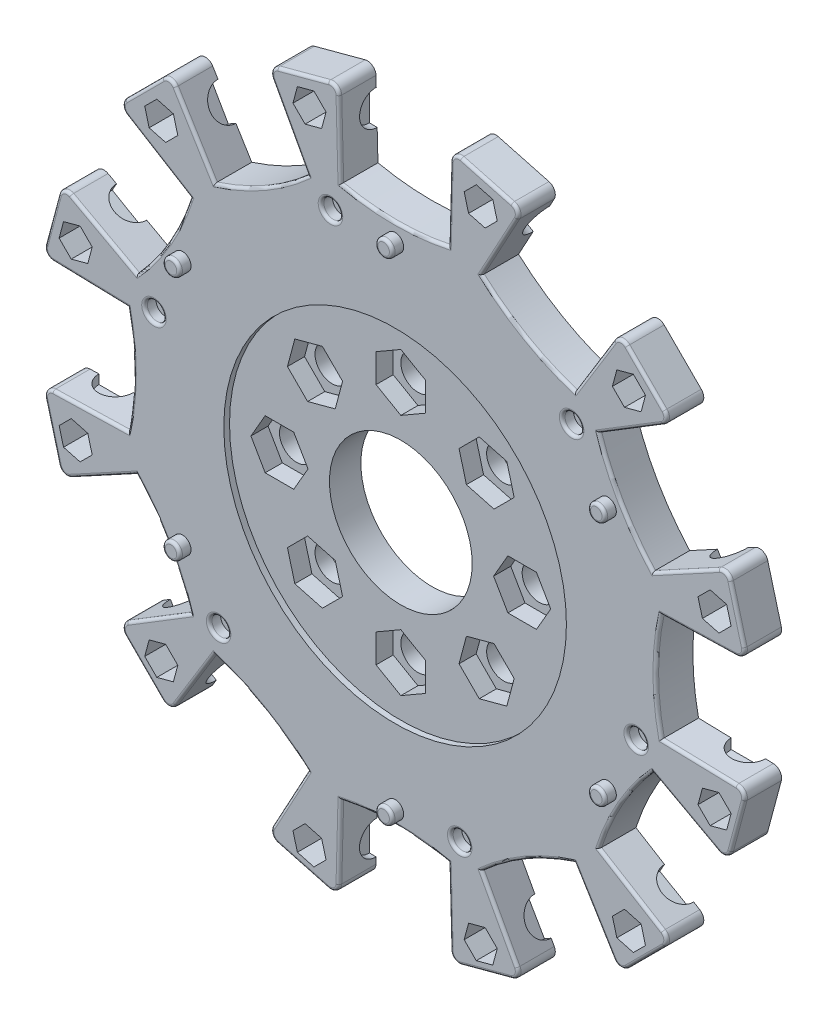
SolidWorks part; units mm, degrees
ref_plane "Front Plane" through (0, 0, 0) normal (0, 0, 1) x (1, 0, 0)
ref_plane "Top Plane" through (0, 0, 0) normal (0, 1, 0) x (1, 0, 0)
ref_plane "Right Plane" through (0, 0, 0) normal (1, 0, 0) x (0, 0, -1)
sketch "Sketch1" plane through (0, 0, 0) normal (0, 0, 1) x (1, 0, 0)
  line L0 (-87.8157, 0) -> (95.9972, 0) construction
  line L1 (0, 160.1388) -> (0, -68.1388) construction
  line L2 (-22.4547, 58.688) -> (-9.8977, 62.0527)
  line L3 (-15.2988, 45.505) -> (-9.5033, 47.0579) construction
  line L4 (-9.8977, 62.0527) -> (-9.5033, 47.0579)
  line L5 (-22.4547, 58.688) -> (-15.2988, 45.505)
  line L6 (22.2778, 58.688) -> (15.1219, 45.505)
  line L7 (9.7207, 62.0527) -> (22.2778, 58.688)
  line L8 (9.7207, 62.0527) -> (9.3264, 47.0579)
  line L9 (48.4602, 39.6864) -> (35.6715, 31.8475)
  line L10 (39.2678, 48.8788) -> (48.4602, 39.6864)
  line L11 (39.2678, 48.8788) -> (31.4289, 36.0901)
  line L12 (61.6341, 10.1394) -> (46.6392, 9.745)
  line L13 (58.2694, 22.6964) -> (61.6341, 10.1394)
  line L14 (58.2694, 22.6964) -> (45.0863, 15.5405)
  line L15 (58.2694, -22.0361) -> (45.0863, -14.8802)
  line L16 (61.6341, -9.479) -> (58.2694, -22.0361)
  line L17 (61.6341, -9.479) -> (46.6392, -9.0847)
  line L18 (39.2678, -48.2185) -> (31.4289, -35.4298)
  line L19 (48.4602, -39.0261) -> (39.2678, -48.2185)
  line L20 (48.4602, -39.0261) -> (35.6715, -31.1872)
  line L21 (9.7207, -61.3923) -> (9.3264, -46.3975)
  line L22 (22.2778, -58.0277) -> (9.7207, -61.3923)
  line L23 (22.2778, -58.0277) -> (15.1219, -44.8446)
  line L24 (-22.4547, -58.0277) -> (-15.2988, -44.8446)
  line L25 (-9.8977, -61.3923) -> (-22.4547, -58.0277)
  line L26 (-9.8977, -61.3923) -> (-9.5033, -46.3975)
  line L27 (-48.6371, -39.0261) -> (-35.8484, -31.1872)
  line L28 (-39.4447, -48.2185) -> (-48.6371, -39.0261)
  line L29 (-39.4447, -48.2185) -> (-31.6058, -35.4298)
  line L30 (-61.811, -9.479) -> (-46.8162, -9.0847)
  line L31 (-58.4463, -22.0361) -> (-61.811, -9.479)
  line L32 (-58.4463, -22.0361) -> (-45.2633, -14.8802)
  line L33 (-58.4463, 22.6964) -> (-45.2633, 15.5405)
  line L34 (-61.811, 10.1394) -> (-58.4463, 22.6964)
  line L35 (-61.811, 10.1394) -> (-46.8162, 9.745)
  line L36 (-39.4447, 48.8788) -> (-31.6058, 36.0901)
  line L37 (-48.6371, 39.6864) -> (-39.4447, 48.8788)
  line L38 (-48.6371, 39.6864) -> (-35.8484, 31.8475)
  line L39 (12.8679, 53.8194) -> (15.7657, 53.0429)
  line L40 (-12.0915, 56.7171) -> (-14.2128, 58.8385)
  line L41 (-14.2128, 58.8385) -> (-17.1106, 58.062)
  line L42 (-17.1106, 58.062) -> (-17.887, 55.1642)
  line L43 (-17.887, 55.1642) -> (-15.7657, 53.0429)
  line L44 (-15.7657, 53.0429) -> (-12.8679, 53.8194)
  line L45 (-12.8679, 53.8194) -> (-12.0915, 56.7171)
  line L46 (15.7657, 53.0429) -> (17.887, 55.1642)
  line L47 (17.887, 55.1642) -> (17.1106, 58.062)
  line L48 (17.1106, 58.062) -> (14.2128, 58.8385)
  line L49 (14.2128, 58.8385) -> (12.0915, 56.7171)
  line L50 (12.0915, 56.7171) -> (12.8679, 53.8194)
  line L51 (38.0536, 40.175) -> (40.175, 38.0536)
  line L52 (40.175, 38.0536) -> (43.0727, 38.8301)
  line L53 (43.0727, 38.8301) -> (43.8492, 41.7279)
  line L54 (43.8492, 41.7279) -> (41.7279, 43.8492)
  line L55 (41.7279, 43.8492) -> (38.8301, 43.0727)
  line L56 (38.8301, 43.0727) -> (38.0536, 40.175)
  line L57 (53.0429, 15.7657) -> (53.8194, 12.8679)
  line L58 (53.8194, 12.8679) -> (56.7171, 12.0915)
  line L59 (56.7171, 12.0915) -> (58.8385, 14.2128)
  line L60 (58.8385, 14.2128) -> (58.062, 17.1106)
  line L61 (58.062, 17.1106) -> (55.1642, 17.887)
  line L62 (55.1642, 17.887) -> (53.0429, 15.7657)
  line L63 (53.8194, -12.8679) -> (53.0429, -15.7657)
  line L64 (53.0429, -15.7657) -> (55.1642, -17.887)
  line L65 (55.1642, -17.887) -> (58.062, -17.1106)
  line L66 (58.062, -17.1106) -> (58.8385, -14.2128)
  line L67 (58.8385, -14.2128) -> (56.7171, -12.0915)
  line L68 (56.7171, -12.0915) -> (53.8194, -12.8679)
  line L69 (40.175, -38.0536) -> (38.0536, -40.175)
  line L70 (38.0536, -40.175) -> (38.8301, -43.0727)
  line L71 (38.8301, -43.0727) -> (41.7279, -43.8492)
  line L72 (41.7279, -43.8492) -> (43.8492, -41.7279)
  line L73 (43.8492, -41.7279) -> (43.0727, -38.8301)
  line L74 (43.0727, -38.8301) -> (40.175, -38.0536)
  line L75 (15.7657, -53.0429) -> (12.8679, -53.8194)
  line L76 (12.8679, -53.8194) -> (12.0915, -56.7171)
  line L77 (12.0915, -56.7171) -> (14.2128, -58.8385)
  line L78 (14.2128, -58.8385) -> (17.1106, -58.062)
  line L79 (17.1106, -58.062) -> (17.887, -55.1642)
  line L80 (17.887, -55.1642) -> (15.7657, -53.0429)
  line L81 (-12.8679, -53.8194) -> (-15.7657, -53.0429)
  line L82 (-15.7657, -53.0429) -> (-17.887, -55.1642)
  line L83 (-17.887, -55.1642) -> (-17.1106, -58.062)
  line L84 (-17.1106, -58.062) -> (-14.2128, -58.8385)
  line L85 (-14.2128, -58.8385) -> (-12.0915, -56.7171)
  line L86 (-12.0915, -56.7171) -> (-12.8679, -53.8194)
  line L87 (-38.0536, -40.175) -> (-40.175, -38.0536)
  line L88 (-40.175, -38.0536) -> (-43.0727, -38.8301)
  line L89 (-43.0727, -38.8301) -> (-43.8492, -41.7279)
  line L90 (-43.8492, -41.7279) -> (-41.7279, -43.8492)
  line L91 (-41.7279, -43.8492) -> (-38.8301, -43.0727)
  line L92 (-38.8301, -43.0727) -> (-38.0536, -40.175)
  line L93 (-53.0429, -15.7657) -> (-53.8194, -12.8679)
  line L94 (-53.8194, -12.8679) -> (-56.7171, -12.0915)
  line L95 (-56.7171, -12.0915) -> (-58.8385, -14.2128)
  line L96 (-58.8385, -14.2128) -> (-58.062, -17.1106)
  line L97 (-58.062, -17.1106) -> (-55.1642, -17.887)
  line L98 (-55.1642, -17.887) -> (-53.0429, -15.7657)
  line L99 (-53.8194, 12.8679) -> (-53.0429, 15.7657)
  line L100 (-53.0429, 15.7657) -> (-55.1642, 17.887)
  line L101 (-55.1642, 17.887) -> (-58.062, 17.1106)
  line L102 (-58.062, 17.1106) -> (-58.8385, 14.2128)
  line L103 (-58.8385, 14.2128) -> (-56.7171, 12.0915)
  line L104 (-56.7171, 12.0915) -> (-53.8194, 12.8679)
  line L105 (-40.175, 38.0536) -> (-38.0536, 40.175)
  line L106 (-38.0536, 40.175) -> (-38.8301, 43.0727)
  line L107 (-38.8301, 43.0727) -> (-41.7279, 43.8492)
  line L108 (-41.7279, 43.8492) -> (-43.8492, 41.7279)
  line L109 (-43.8492, 41.7279) -> (-43.0727, 38.8301)
  line L110 (-43.0727, 38.8301) -> (-40.175, 38.0536)
  circle A0 centre (0, 0) radius 62.5 construction
  arc A2 (-9.5033, 47.0579) -> (9.3264, 47.0579) centre (-0.0885, 91.062) ccw
  arc A3 (15.1219, 45.505) -> (31.4289, 36.0901) centre (45.2774, 78.9062) ccw
  arc A4 (35.6715, 31.8475) -> (45.0863, 15.5405) centre (78.4876, 45.6961) ccw
  arc A5 (46.6392, 9.745) -> (46.6392, -9.0847) centre (90.6433, 0.3302) ccw
  arc A6 (45.0863, -14.8802) -> (35.6715, -31.1872) centre (78.4876, -45.0357) ccw
  arc A7 (31.4289, -35.4298) -> (15.1219, -44.8446) centre (45.2774, -78.2459) ccw
  arc A8 (9.3264, -46.3975) -> (-9.5033, -46.3975) centre (-0.0885, -90.4016) ccw
  arc A9 (-15.2988, -44.8446) -> (-31.6058, -35.4298) centre (-45.4544, -78.2459) ccw
  arc A10 (-35.8484, -31.1872) -> (-45.2633, -14.8802) centre (-78.6645, -45.0357) ccw
  arc A11 (-46.8162, -9.0847) -> (-46.8162, 9.745) centre (-90.8203, 0.3302) ccw
  arc A12 (-45.2633, 15.5405) -> (-35.8484, 31.8475) centre (-78.6645, 45.6961) ccw
  arc A13 (-31.6058, 36.0901) -> (-15.2988, 45.505) centre (-45.4544, 78.9062) ccw
  circle A14 centre (-14.9893, 55.9407) radius 2.5981 construction
  point P10 (-16.1762, 60.3704)
  point P12 (-16.1762, 60.3704)
  point P14 (-12.4011, 46.2814)
  dimension "D1" = 125
  dimension "D3" = 6
  dimension "D2" = 15
  dimension "D5" = 45
  dimension "D4" = 12
  dimension "D6" = 13
  dimension "D8" = 10
  dimension "D9" = 3
  dimension "D7" = 12
  dimension "D10" = 12
extrude "Boss-Extrude1" add sketch "Sketch1" along normal blind 6.5
sketch "Sketch5" plane through (0, 0, 0) normal (0, 0, -1) x (-1, 0, 0)
  line L0 (0, 0) -> (0, 67.5888) construction
  line L2 (-11, 58.3612) -> (11, 58.3612)
  line L3 (-11, 58.3612) -> (-11, 55.3612)
  line L4 (-11, 55.3612) -> (11, 55.3612)
  line L5 (11, 58.3612) -> (11, 55.3612)
  point P3 (0, 56.8612)
  dimension "D1" = 22
  dimension "D2" = 3
revolve "Cut-Revolve2" cut sketch "Sketch5" angle 360 about L4
fillet "Fillet1" radius 1.5 24 edges at (9.7207, 62.0527, 3.25) (22.2778, 58.688, 3.25) (39.2678, 48.8788, 3.25) (48.4602, 39.6864, 3.25) (58.2694, 22.6964, 3.25) (61.6341, 10.1394, 3.25) (61.6341, -9.479, 3.25) (58.2694, -22.0361, 3.25) (48.4602, -39.0261, 3.25) (39.2678, -48.2185, 3.25) (22.2778, -58.0277, 3.25) (9.7207, -61.3923, 3.25) (-9.8977, -61.3923, 3.25) (-22.4547, -58.0277, 3.25) (-39.4447, -48.2185, 3.25) (-48.6371, -39.0261, 3.25) (-58.4463, -22.0361, 3.25) (-61.811, -9.479, 3.25) (-61.811, 10.1394, 3.25) (-58.4463, 22.6964, 3.25) (-48.6371, 39.6864, 3.25) (-39.4447, 48.8788, 3.25) (-22.4547, 58.688, 3.25) (-9.8977, 62.0527, 3.25)
sketch "Sketch6" plane through (0, 0, 6.5) normal (0, 0, 1) x (1, 0, 0)
  line L0 (0, 12.5) -> (0, 30) construction
  line L1 (19.8556, 13.7319) -> (18.5616, 18.5616)
  line L2 (4.3301, 23.75) -> (0, 26.25)
  line L3 (0, 26.25) -> (-4.3301, 23.75)
  line L4 (-4.3301, 23.75) -> (-4.3301, 18.75)
  line L5 (-4.3301, 18.75) -> (0, 16.25)
  line L6 (0, 16.25) -> (4.3301, 18.75)
  line L7 (4.3301, 18.75) -> (4.3301, 23.75)
  line L8 (18.5616, 18.5616) -> (13.7319, 19.8556)
  line L9 (13.7319, 19.8556) -> (10.1964, 16.3201)
  line L10 (10.1964, 16.3201) -> (11.4905, 11.4905)
  line L11 (11.4905, 11.4905) -> (16.3201, 10.1964)
  line L12 (16.3201, 10.1964) -> (19.8556, 13.7319)
  line L13 (23.75, -4.3301) -> (26.25, 0)
  line L14 (26.25, 0) -> (23.75, 4.3301)
  line L15 (23.75, 4.3301) -> (18.75, 4.3301)
  line L16 (18.75, 4.3301) -> (16.25, 0)
  line L17 (16.25, 0) -> (18.75, -4.3301)
  line L18 (18.75, -4.3301) -> (23.75, -4.3301)
  line L19 (13.7319, -19.8556) -> (18.5616, -18.5616)
  line L20 (18.5616, -18.5616) -> (19.8556, -13.7319)
  line L21 (19.8556, -13.7319) -> (16.3201, -10.1964)
  line L22 (16.3201, -10.1964) -> (11.4905, -11.4905)
  line L23 (11.4905, -11.4905) -> (10.1964, -16.3201)
  line L24 (10.1964, -16.3201) -> (13.7319, -19.8556)
  line L25 (-4.3301, -23.75) -> (0, -26.25)
  line L26 (0, -26.25) -> (4.3301, -23.75)
  line L27 (4.3301, -23.75) -> (4.3301, -18.75)
  line L28 (4.3301, -18.75) -> (0, -16.25)
  line L29 (0, -16.25) -> (-4.3301, -18.75)
  line L30 (-4.3301, -18.75) -> (-4.3301, -23.75)
  line L31 (-19.8556, -13.7319) -> (-18.5616, -18.5616)
  line L32 (-18.5616, -18.5616) -> (-13.7319, -19.8556)
  line L33 (-13.7319, -19.8556) -> (-10.1964, -16.3201)
  line L34 (-10.1964, -16.3201) -> (-11.4905, -11.4905)
  line L35 (-11.4905, -11.4905) -> (-16.3201, -10.1964)
  line L36 (-16.3201, -10.1964) -> (-19.8556, -13.7319)
  line L37 (-23.75, 4.3301) -> (-26.25, 0)
  line L38 (-26.25, 0) -> (-23.75, -4.3301)
  line L39 (-23.75, -4.3301) -> (-18.75, -4.3301)
  line L40 (-18.75, -4.3301) -> (-16.25, 0)
  line L41 (-16.25, 0) -> (-18.75, 4.3301)
  line L42 (-18.75, 4.3301) -> (-23.75, 4.3301)
  line L43 (-13.7319, 19.8556) -> (-18.5616, 18.5616)
  line L44 (-18.5616, 18.5616) -> (-19.8556, 13.7319)
  line L45 (-19.8556, 13.7319) -> (-16.3201, 10.1964)
  line L46 (-16.3201, 10.1964) -> (-11.4905, 11.4905)
  line L47 (-11.4905, 11.4905) -> (-10.1964, 16.3201)
  line L48 (-10.1964, 16.3201) -> (-13.7319, 19.8556)
  circle A0 centre (0, 0) radius 12.5
  circle A1 centre (0, 0) radius 30
  circle A2 centre (0, 21.25) radius 4.3301 construction
  circle A3 centre (0, 21.25) radius 3
  circle A4 centre (15.026, 15.026) radius 3
  circle A5 centre (21.25, 0) radius 3
  circle A6 centre (15.026, -15.026) radius 3
  circle A7 centre (0, -21.25) radius 3
  circle A8 centre (-15.026, -15.026) radius 3
  circle A9 centre (-21.25, 0) radius 3
  circle A10 centre (-15.026, 15.026) radius 3
  dimension "D1" = 60
  dimension "D2" = 25
  dimension "D4" = 6
  dimension "D5" = 5
  dimension "D3" = 8
  dimension "D6" = 8
extrude "Cut-Extrude1" cut sketch "Sketch6" against normal through all contours A0 | A3 | A4 | A5 | A6 | A7 | A8 | A9 | A10 region at (0, 0, 6.5) region at (0, 21.25, 6.5) region at (15.026, 15.026, 6.5) region at (21.25, 0, 6.5) region at (15.026, -15.026, 6.5) region at (0, -21.25, 6.5) region at (-15.026, -15.026, 6.5) region at (-21.25, 0, 6.5) region at (-15.026, 15.026, 6.5)
extrude "Cut-Extrude2" cut sketch "Sketch6<3>" against normal blind 1 contours A1 L7 L6 L5 L4 L3 L2 L12 L11 L10 L9 L8 L1 L18 L17 L16 L15 L14 L13 L24 L23 L22 L21 L20 L19 L30 L29 L28 L27 L26 L25 L36 L35 L34 L33 L32 L31 L42 L41 L40 L39 L38 L37 region at (-29.1515, 0, 6.5)
sketch "Sketch6<3>" plane through (0, 0, 6.5) normal (0, 0, 1) x (1, 0, 0) same geometry as "Sketch6"
extrude "Cut-Extrude3" cut sketch "Sketch6<4>" against normal blind 4 contours L6 L7 L2 L3 L4 L5 A3 | L11 L12 L1 L8 L9 L10 A4 | L17 L18 L13 L14 L15 L16 A5 | L23 L24 L19 L20 L21 L22 A6 | L29 L30 L25 L26 L27 L28 A7 | L35 L36 L31 L32 L33 L34 A8 | L41 L42 L37 L38 L39 L40 A9 | L47 L48 L43 L44 L45 L46 A10 region at (17.9913, 12.0607, 6.5) region at (4.1978, 21.25, 6.5) region at (21.25, -4.1978, 6.5) region at (12.0607, -17.9913, 6.5) region at (-4.1978, -21.25, 6.5) region at (-17.9913, -12.0607, 6.5) region at (-21.25, 4.1978, 6.5) region at (-12.0607, 17.9913, 6.5)
sketch "Sketch6<4>" plane through (0, 0, 6.5) normal (0, 0, 1) x (1, 0, 0) same geometry as "Sketch6"
pattern_circular "CirPattern1" count 12 over 360 about axis through (0, 0, 0) along (0, 0, 1) of "Cut-Revolve2"
sketch "Sketch7" plane through (0, 0, 6.5) normal (0, 0, 1) x (1, 0, 0)
  circle A0 centre (0, 43) radius 1.5
  circle A1 centre (37.2391, 21.5) radius 1.5
  circle A2 centre (37.2391, -21.5) radius 1.5
  circle A3 centre (0, -43) radius 1.5
  circle A4 centre (-37.2391, -21.5) radius 1.5
  circle A5 centre (-37.2391, 21.5) radius 1.5
  dimension "D1" = 3
  dimension "D2" = 43
  dimension "D3" = 6
extrude "Boss-Extrude2" add sketch "Sketch7" along normal blind 2
fillet "Fillet2" radius 0.5 6 edges at (-35.7391, 21.5, 8.5) (-35.7391, -21.5, 8.5) (1.5, -43, 8.5) (38.7391, -21.5, 8.5) (38.7391, 21.5, 8.5) (1.5, 43, 8.5)
sketch "Sketch8" plane through (0, 0, 6.5) normal (0, 0, 1) x (1, 0, 0)
  line L0 (0, 0) -> (-15.6617, 58.4502) construction
  line L1 (-14.2128, 58.8385) -> (-17.1106, 58.062) construction
  circle A0 centre (-11.3138, 42.2238) radius 1.65
  circle A1 centre (30.9099, 30.9099) radius 1.65
  circle A2 centre (42.2238, -11.3138) radius 1.65
  circle A3 centre (11.3138, -42.2238) radius 1.65
  circle A4 centre (-30.9099, -30.9099) radius 1.65
  circle A5 centre (-42.2238, 11.3138) radius 1.65
  dimension "D1" = 3.3
  dimension "D2" = 6
extrude "Cut-Extrude4" cut sketch "Sketch8" against normal blind 2
fillet "Fillet3" radius 0.5 6 edges at (-40.5738, 11.3138, 6.5) (-29.2599, -30.9099, 6.5) (12.9638, -42.2238, 6.5) (43.8738, -11.3138, 6.5) (32.5599, 30.9099, 6.5) (-9.6638, 42.2238, 6.5)
fillet "Fillet5" radius 0.5 72 edges at (21.43, 58.3238, 6.5) (18.246, 51.2605, 6.5) (22.7774, 39.9351, 6.5) (34.8512, 41.6735, 6.5) (39.3762, 47.9625, 6.5) (43.864, 44.2826, 6.5) (47.5439, 39.7948, 6.5) (41.2548, 35.2698, 6.5) (39.5164, 23.1961, 6.5) (50.8418, 18.6647, 6.5) (57.9051, 21.8486, 6.5) (59.9517, 16.4179, 6.5) (60.8947, 10.6914, 6.5) (53.1857, 9.9172, 6.5) (45.6433, 0.3302, 6.5) (53.1857, -9.2568, 6.5) (60.8947, -10.0311, 6.5) (59.9517, -15.7576, 6.5) (57.9051, -21.1883, 6.5) (50.8418, -18.0043, 6.5) (39.5164, -22.5357, 6.5) (41.2548, -34.6095, 6.5) (47.5439, -39.1345, 6.5) (43.864, -43.6223, 6.5) (39.3762, -47.3022, 6.5) (34.8512, -41.0131, 6.5) (22.7774, -39.2747, 6.5) (18.246, -50.6001, 6.5) (21.43, -57.6634, 6.5) (15.9993, -59.71, 6.5) (10.2728, -60.653, 6.5) (9.4985, -52.944, 6.5) (-0.0885, -45.4016, 6.5) (-9.6755, -52.944, 6.5) (-10.4497, -60.653, 6.5) (-16.1762, -59.71, 6.5) (-21.6069, -57.6634, 6.5) (-18.423, -50.6001, 6.5) (-22.9544, -39.2747, 6.5) (-35.0281, -41.0131, 6.5) (-39.5531, -47.3022, 6.5) (-44.0409, -43.6223, 6.5) (-47.7208, -39.1345, 6.5) (-41.4318, -34.6095, 6.5) (-39.6934, -22.5357, 6.5) (-51.0188, -18.0043, 6.5) (-58.0821, -21.1883, 6.5) (-60.1287, -15.7576, 6.5) (-61.0716, -10.0311, 6.5) (-53.3627, -9.2568, 6.5) (-45.8203, 0.3302, 6.5) (-53.3627, 9.9172, 6.5) (-61.0716, 10.6914, 6.5) (-60.1287, 16.4179, 6.5) (-58.0821, 21.8486, 6.5) (-51.0188, 18.6647, 6.5) (-39.6934, 23.1961, 6.5) (-41.4318, 35.2698, 6.5) (-47.7208, 39.7948, 6.5) (-44.0409, 44.2826, 6.5) (-39.5531, 47.9625, 6.5) (-35.0281, 41.6735, 6.5) (-22.9544, 39.9351, 6.5) (-18.423, 51.2605, 6.5) (-21.6069, 58.3238, 6.5) (-16.1762, 60.3704, 6.5) (-10.4497, 61.3133, 6.5) (-9.6755, 53.6044, 6.5) (-0.0885, 46.062, 6.5) (10.2728, 61.3133, 6.5) (15.9993, 60.3704, 6.5) (9.4985, 53.6044, 6.5)
